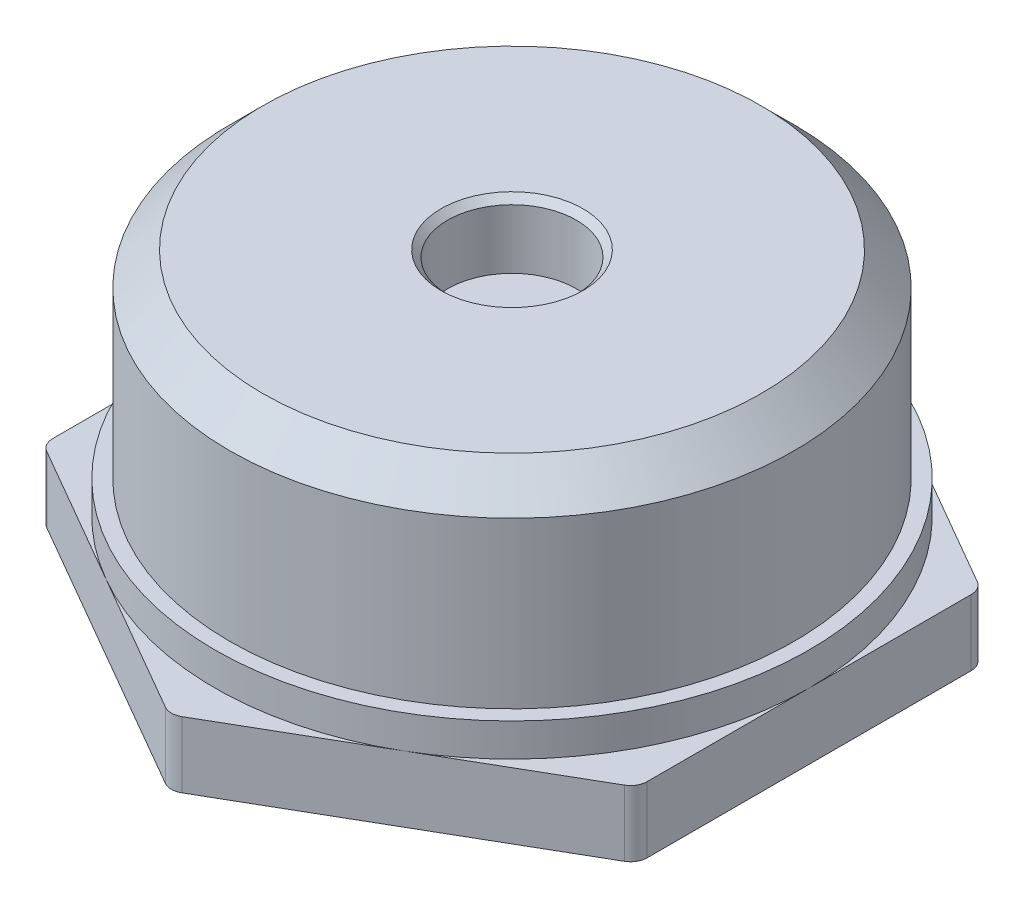
SolidWorks part; units mm, degrees
material "ABS"
ref_plane "Front Plane" through (0, 0, 0) normal (0, 0, 1) x (1, 0, 0)
ref_plane "Top Plane" through (0, 0, 0) normal (0, 1, 0) x (1, 0, 0)
ref_plane "Right Plane" through (0, 0, 0) normal (1, 0, 0) x (0, 0, -1)
ref_plane "Plane2" through (0, 31, 0) normal (0, 1, 0) x (1, 0, 0)
sketch "Sketch1" plane through (0, 31, 0) normal (0, 1, 0) x (1, 0, 0)
  line L1 (0, 10.3923) -> (-9, 5.1962)
  line L2 (-9, 5.1962) -> (-9, -5.1962)
  line L3 (-9, -5.1962) -> (0, -10.3923)
  line L4 (0, -10.3923) -> (9, -5.1962)
  line L5 (9, -5.1962) -> (9, 5.1962)
  line L6 (9, 5.1962) -> (0, 10.3923)
  circle A0 centre (0, 0) radius 9 construction
  dimension "D1" = 18
extrude "Boss-Extrude1" add sketch "Sketch1" along normal blind 2
fillet "Fillet1" radius 0.5 6 edges at (0, 32, -10.3923) (-9, 32, -5.1962) (-9, 32, 5.1962) (0, 32, 10.3923) (9, 32, 5.1962) (9, 32, -5.1962)
sketch "Sketch2" plane through (0, 33, 0) normal (0, 1, 0) x (1, 0, 0)
  circle A1 centre (0, 0) radius 9
  dimension "D2" = 18
extrude "Boss-Extrude2" add sketch "Sketch2" along normal blind 1 contours A1
sketch "Sketch3" plane through (0, 34, 0) normal (0, 1, 0) x (1, 0, 0)
  circle A0 centre (0, 0) radius 8.55
  dimension "D1" = 17.1
extrude "Boss-Extrude3" add sketch "Sketch3" along normal blind 4
sketch "Sketch4" plane through (0, 38, 0) normal (0, 1, 0) x (1, 0, 0)
  line L1 (0, 2.8868) -> (-2.5, 1.4434)
  line L2 (-2.5, 1.4434) -> (-2.5, -1.4434)
  line L3 (-2.5, -1.4434) -> (0, -2.8868)
  line L4 (0, -2.8868) -> (2.5, -1.4434)
  line L5 (2.5, -1.4434) -> (2.5, 1.4434)
  line L6 (2.5, 1.4434) -> (0, 2.8868)
  circle A0 centre (0, 0) radius 2.5 construction
  dimension "D1" = 5
extrude "Cut-Extrude1" cut sketch "Sketch4" against normal through all
sketch "Sketch5" plane through (0, 38, 0) normal (0, 1, 0) x (1, 0, 0)
  circle A0 centre (0, 0) radius 8.55
  circle A1 centre (0, 0) radius 8.55 construction
extrude "Boss-Extrude4" add sketch "Sketch5" along normal blind 1 and the other way blind 1
sketch "Sketch6" plane through (0, 39, 0) normal (0, 1, 0) x (1, 0, 0)
  circle A1 centre (0, 0) radius 8.55
  circle A2 centre (0, 0) radius 8.55 construction
extrude "Boss-Extrude5" add sketch "Sketch6" along normal blind 1
chamfer "Chamfer2" distance 1 angle 45 1 edges at (0, 40, 8.55)
sketch "Sketch7" plane through (0, 40, 0) normal (0, 1, 0) x (1, 0, 0)
  circle A0 centre (0, 0) radius 1.95
  dimension "D1" = 3.9
extrude "Cut-Extrude2" cut sketch "Sketch7" against normal blind 2
chamfer "Chamfer3" distance 0.2 angle 45 1 edges at (0, 40, 1.95)
